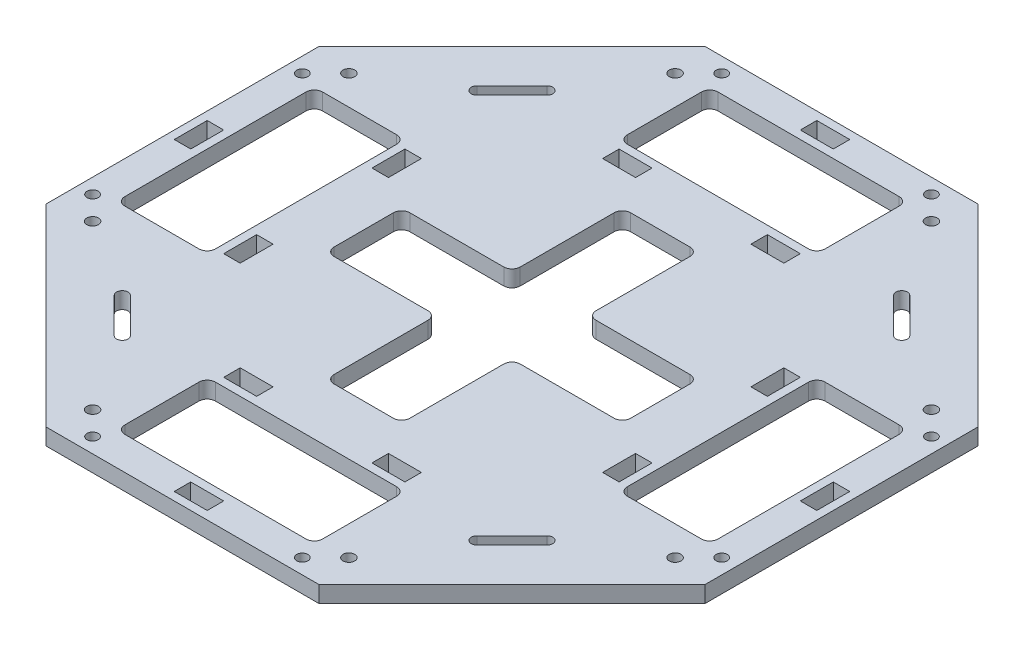
SolidWorks part; units mm, degrees
material "Custom Plastic"
ref_plane "Front Plane" through (0, 0, 0) normal (0, 0, 1) x (1, 0, 0)
ref_plane "Top Plane" through (0, 0, 0) normal (0, 1, 0) x (1, 0, 0)
ref_plane "Right Plane" through (0, 0, 0) normal (1, 0, 0) x (0, 0, -1)
ref_axis "Axis1" through (0, -0.2997, 0) along (0, 1, 0)
sketch "Base sketch" plane through (0, 0, 0) normal (0, 1, 0) x (1, 0, 0)
  line L1 (-127, 52.6051) -> (-127, -52.6051)
  line L2 (-127, -52.6051) -> (-52.6051, -127)
  line L3 (-52.6051, -127) -> (52.6051, -127)
  line L4 (52.6051, -127) -> (127, -52.6051)
  line L5 (127, -52.6051) -> (127, 52.6051)
  line L6 (127, 52.6051) -> (52.6051, 127)
  line L7 (52.6051, 127) -> (-52.6051, 127)
  line L8 (-52.6051, 127) -> (-127, 52.6051)
  circle A0 centre (0, 0) radius 127 construction
  dimension "D1" = 254
extrude "Base" add sketch "Base sketch" along normal blind 6.35
sketch "Sketch3" plane through (0, 6.35, 0) normal (0, 1, 0) x (1, 0, 0)
  line L0 (52.6051, 127) -> (-52.6051, 127) construction
  line L1 (-38.1, 114.3) -> (38.1, 114.3)
  line L2 (-38.1, 114.3) -> (-38.1, 79.375)
  line L4 (-38.1, 79.375) -> (38.1, 79.375)
  line L5 (38.1, 114.3) -> (38.1, 79.375)
  point P6 (0, 79.375)
  dimension "D1" = 76.2
  dimension "D2" = 34.925
  dimension "D3" = 12.7
extrude "Wheel cutout" cut sketch "Sketch3" against normal up to next
fillet "Wheel cutout fillets" radius 3.175 4 edges at (38.1, 3.175, -114.3) (38.1, 3.175, -79.375) (-38.1, 3.175, -79.375) (-38.1, 3.175, -114.3)
pattern_circular "Wheel cutout pattern" count 4 over 360 about axis through (0, -0.2997, 0) along (0, 1, 0) of "Wheel cutout", "Wheel cutout fillets"
sketch "Sketch4" plane through (0, 6.35, 0) normal (0, 1, 0) x (1, 0, 0)
  line L0 (0, 0) -> (0, 127) construction
  line L1 (52.6051, 127) -> (-52.6051, 127) construction
  line L2 (34.925, 120.65) -> (-34.925, 120.65) construction
  line L3 (-34.925, 123.825) -> (-22.225, 123.825) construction
  line L4 (-34.925, 123.825) -> (-34.925, 117.475) construction
  line L5 (-34.925, 117.475) -> (-22.225, 117.475) construction
  line L6 (-22.225, 123.825) -> (-22.225, 117.475) construction
  line L7 (-34.925, 123.825) -> (-22.225, 117.475) construction
  line L8 (-34.925, 117.475) -> (-22.225, 123.825) construction
  line L9 (34.925, 114.3) -> (-34.925, 114.3) construction
  line L10 (34.925, 117.475) -> (22.225, 123.825) construction
  line L11 (34.925, 123.825) -> (22.225, 117.475) construction
  line L12 (22.225, 123.825) -> (22.225, 117.475) construction
  line L13 (34.925, 117.475) -> (22.225, 117.475) construction
  line L14 (34.925, 123.825) -> (34.925, 117.475) construction
  line L15 (34.925, 123.825) -> (22.225, 123.825) construction
  line L16 (-38.1, 96.8375) -> (38.1, 96.8375) construction
  line L17 (-38.1, 111.125) -> (-38.1, 82.55) construction
  line L18 (38.1, 82.55) -> (38.1, 111.125) construction
  line L19 (34.925, 69.85) -> (22.225, 76.2) construction
  line L20 (34.925, 76.2) -> (22.225, 69.85) construction
  line L21 (-34.925, 76.2) -> (-22.225, 69.85) construction
  line L22 (-34.925, 69.85) -> (-22.225, 76.2) construction
  line L23 (34.925, 73.025) -> (-34.925, 73.025) construction
  line L24 (34.925, 69.85) -> (22.225, 69.85)
  line L25 (34.925, 69.85) -> (34.925, 76.2)
  line L26 (34.925, 76.2) -> (22.225, 76.2)
  line L27 (22.225, 69.85) -> (22.225, 76.2)
  line L28 (-22.225, 69.85) -> (-22.225, 76.2)
  line L29 (-34.925, 76.2) -> (-22.225, 76.2)
  line L30 (-34.925, 69.85) -> (-34.925, 76.2)
  line L31 (-34.925, 69.85) -> (-22.225, 69.85)
  line L33 (-6.35, 117.475) -> (6.35, 117.475)
  line L34 (-6.35, 117.475) -> (-6.35, 123.825)
  line L35 (-6.35, 123.825) -> (6.35, 123.825)
  line L36 (6.35, 117.475) -> (6.35, 123.825)
  line L37 (-6.35, 117.475) -> (6.35, 123.825) construction
  line L38 (-6.35, 123.825) -> (6.35, 117.475) construction
  point P5 (-28.575, 120.65)
  point P12 (0, 120.65)
  point P17 (28.575, 120.65)
  point P34 (28.575, 73.025)
  point P35 (-28.575, 73.025)
  point P38 (0, 120.65)
  dimension "D1" = 6.35
  dimension "D2" = 12.7
  dimension "D3" = 69.85
  dimension "D4" = 6.35
  dimension "D5" = 12.7
  dimension "D6" = 6.35
extrude "Support cutouts" cut sketch "Sketch4" against normal up to next
pattern_circular "Support cutout pattern" count 4 over 360 about axis through (0, -0.2997, 0) along (0, 1, 0) of "Support cutouts"
sketch "Sketch5" plane through (0, 6.35, 0) normal (0, 1, 0) x (1, 0, 0)
  line L0 (14.605, 57.15) -> (-14.605, 57.15)
  line L1 (-14.605, 57.15) -> (-14.605, 14.605)
  line L2 (0, 0) -> (0, 57.15) construction
  line L3 (14.605, 14.605) -> (14.605, 57.15)
  line L4 (0, 0) -> (-89.8026, 89.8026) construction
  line L5 (127, 52.6051) -> (52.6051, 127) construction
  line L6 (89.8026, 89.8026) -> (0, 0) construction
  line L7 (-52.6051, 127) -> (-127, 52.6051) construction
  line L8 (22.225, 69.85) -> (34.925, 69.85) construction
  line L9 (-14.605, 14.605) -> (0, 0)
  line L10 (0, 0) -> (14.605, 14.605)
  dimension "D1" = 12.7
  dimension "D2" = 29.21
extrude "Motor Clearance" cut sketch "Sketch5" against normal through all
pattern_circular "CirPattern1" count 4 every 90 about axis through (0, -0.2997, 0) along (0, 1, 0) of "Motor Clearance"
fillet "Fillet1" radius 3.175 12 edges at (-14.605, 3.175, 57.15) (-57.15, 3.175, 14.605) (14.605, 3.175, 57.15) (-14.605, 3.175, 14.605) (14.605, 3.175, 14.605) (14.605, 3.175, -14.605) (57.15, 3.175, 14.605) (57.15, 3.175, -14.605) (14.605, 3.175, -57.15) (-14.605, 3.175, -14.605) (-14.605, 3.175, -57.15) (-57.15, 3.175, -14.605)
sketch "Aligner" [suppressed] plane through (0, 6.35, 0) normal (0, 1, 0) x (1, 0, 0)
  line L0 (74.1687, 87.0459) -> (70.2318, 109.3733)
  line L1 (127, 52.6051) -> (52.6051, 127) construction
  line L2 (70.2318, 109.3733) -> (109.3733, 70.2318)
  line L3 (127, 44.45) -> (109.3733, 70.2318)
  line L4 (89.8026, 89.8026) -> (0, 0) construction
  line L5 (87.0459, 74.1687) -> (109.3733, 70.2318)
  line L6 (70.2318, 109.3733) -> (67.4939, 124.9011)
  line L7 (64.9924, 127) -> (44.45, 127)
  line L9 (109.3733, 70.2318) -> (124.9011, 67.4939)
  line L10 (127, 64.9924) -> (127, 44.45)
  line L11 (52.6051, 127) -> (-52.6051, 127) construction
  line L12 (44.45, 127) -> (70.2318, 109.3733)
  line L13 (38.1, 82.55) -> (38.1, 111.125) construction
  arc A0 (74.1687, 87.0459) -> (87.0459, 74.1687) centre (89.8026, 89.8026) ccw
  arc A1 (124.9011, 67.4939) -> (127, 64.9924) centre (124.46, 64.9924) cw
  arc A2 (67.4939, 124.9011) -> (64.9924, 127) centre (64.9924, 124.46) ccw
  dimension "D1" = 15.875
  dimension "D2" = 2.54
  dimension "D3" = 55
  dimension "D5" = 6.35
sketch "Aligner hole sketch" plane through (0, 6.35, 0) normal (0, 1, 0) x (1, 0, 0)
  line L0 (-89.8026, 89.8026) -> (0, 0) construction
  line L1 (-52.6051, 127) -> (-127, 52.6051) construction
  line L2 (-112.2532, 49.3914) -> (-80.8223, 80.8223) construction
  line L3 (-80.8223, 80.8223) -> (-49.3914, 112.2532) construction
  circle A2 centre (-49.3914, 112.2532) radius 2.2479
  circle A3 centre (-112.2532, 49.3914) radius 2.2479
  dimension "D3" = 4.4958
  dimension "D1" = 12.7
  dimension "D2" = 88.9
extrude "Aligner holes" cut sketch "Aligner hole sketch" against normal through all
pattern_circular "Aligner hole pattern" count 4 over 360 about axis through (0, -0.2997, 0) along (0, 1, 0) of "Aligner holes"
sketch "Sketch7" plane through (0, 6.35, 0) normal (0, 1, 0) x (1, 0, 0)
  circle A0 centre (121.2335, 40.4112) radius 2.1526 construction
  circle A1 centre (121.2335, -40.4112) radius 2.1526 construction
  circle A2 centre (40.4112, -121.2335) radius 2.1526 construction
  circle A3 centre (-40.4112, -121.2335) radius 2.1526 construction
  circle A4 centre (-121.2335, -40.4112) radius 2.1526 construction
  circle A5 centre (-121.2335, 40.4112) radius 2.1526 construction
  circle A6 centre (-40.4112, 121.2335) radius 2.1526 construction
  circle A7 centre (40.4112, 121.2335) radius 2.1527 construction
  circle A8 centre (121.2335, 40.4112) radius 2.1526
  circle A9 centre (121.2335, -40.4112) radius 2.1526
  circle A10 centre (40.4112, -121.2335) radius 2.1526
  circle A11 centre (-40.4112, -121.2335) radius 2.1526
  circle A12 centre (-121.2335, -40.4112) radius 2.1526
  circle A13 centre (-121.2335, 40.4112) radius 2.1526
  circle A14 centre (-40.4112, 121.2335) radius 2.1526
  circle A15 centre (40.4112, 121.2335) radius 2.1527
extrude "Cut-Extrude2" cut sketch "Sketch7" against normal through all
sketch "Sketch8" [suppressed] plane through (0, 6.35, 0) normal (0, 1, 0) x (1, 0, 0)
  line L0 (-109.4634, 61.1615) -> (-61.1615, 109.4634)
  line L1 (-55.7414, 107.2183) -> (-55.7414, 74.8894)
  line L2 (-56.6713, 72.6443) -> (-72.6443, 56.6713)
  line L3 (-74.8894, 55.7414) -> (-107.2183, 55.7414)
  line L4 (-52.6051, 127) -> (-127, 52.6051) construction
  line L5 (0, 0) -> (-64.6578, 64.6578) construction
  line L6 (-64.6578, 64.6578) -> (-85.3124, 85.3124) construction
  line L7 (-85.3124, 85.3124) -> (-89.8026, 89.8026) construction
  circle A0 centre (-112.2532, 49.3914) radius 2.2479 construction
  arc A1 (-109.4634, 61.1615) -> (-107.2183, 55.7414) centre (-107.2183, 58.9164) ccw
  arc A2 (-72.6443, 56.6713) -> (-74.8894, 55.7414) centre (-74.8894, 58.9164) cw
  arc A3 (-55.7414, 74.8894) -> (-56.6713, 72.6443) centre (-58.9164, 74.8894) cw
  arc A4 (-61.1615, 109.4634) -> (-55.7414, 107.2183) centre (-58.9164, 107.2183) cw
  dimension "D4" = 3.175
  dimension "D1" = 6.35
  dimension "D2" = 6.35
  dimension "D3" = 29.21
extrude "Aligher Lightenning holes" [suppressed] cut sketch "Sketch8" against normal through all
pattern_circular "CirPattern3" [suppressed] count 4 over 360 about axis through (0, -0.2997, 0) along (0, 1, 0) of bodies 139
sketch "Sketch9" plane through (0, 6.35, 0) normal (0, 1, 0) x (1, 0, 0)
  line L0 (-80.2671, 66.7967) -> (-66.7967, 80.2671) construction
  line L1 (-69.922, 83.3924) -> (-83.3924, 69.922) construction
  line L2 (-80.2671, 66.7967) -> (-66.7967, 80.2671)
  line L3 (-69.922, 83.3924) -> (-83.3924, 69.922)
  line L8 (-52.6051, 127) -> (-127, 52.6051)
  line L9 (-127, 52.6051) -> (-127, -52.6051)
  line L10 (-127, -52.6051) -> (-52.6051, -127)
  line L11 (-52.6051, -127) -> (52.6051, -127)
  line L12 (52.6051, -127) -> (127, -52.6051)
  line L13 (127, -52.6051) -> (127, 52.6051)
  line L14 (127, 52.6051) -> (52.6051, 127)
  line L15 (52.6051, 127) -> (-52.6051, 127)
  line L16 (-52.6051, 127) -> (-127, 52.6051)
  line L17 (-127, 52.6051) -> (-127, -52.6051)
  line L18 (-127, -52.6051) -> (-52.6051, -127)
  line L19 (-52.6051, -127) -> (52.6051, -127)
  line L20 (52.6051, -127) -> (127, -52.6051)
  line L21 (127, -52.6051) -> (127, 52.6051)
  line L22 (127, 52.6051) -> (52.6051, 127)
  line L23 (52.6051, 127) -> (-52.6051, 127)
  arc A0 (-66.7967, 80.2671) -> (-69.922, 83.3924) centre (-68.3593, 81.8297) ccw construction
  arc A1 (-83.3924, 69.922) -> (-80.2671, 66.7967) centre (-81.8297, 68.3593) ccw construction
  arc A2 (-66.7967, 80.2671) -> (-69.922, 83.3924) centre (-68.3593, 81.8297) ccw
  arc A3 (-83.3924, 69.922) -> (-80.2671, 66.7967) centre (-81.8297, 68.3593) ccw
  dimension "D1" = 0
extrude "limit switch mount hole" cut sketch "Sketch9" against normal through all flip side to cut
pattern_circular "limit switch mount hole pattern" count 4 over 360 about axis through (0, -0.2997, 0) along (0, 1, 0) of "limit switch mount hole"
equation "\"MAT_THICKNESS\"=0.25"
equation "\"D1@Sketch4\"=\"MAT_THICKNESS\""
equation "\"D1@Base\"=\"MAT_THICKNESS\""
equation "\"D6@Sketch4\"=\"MAT_THICKNESS\""
